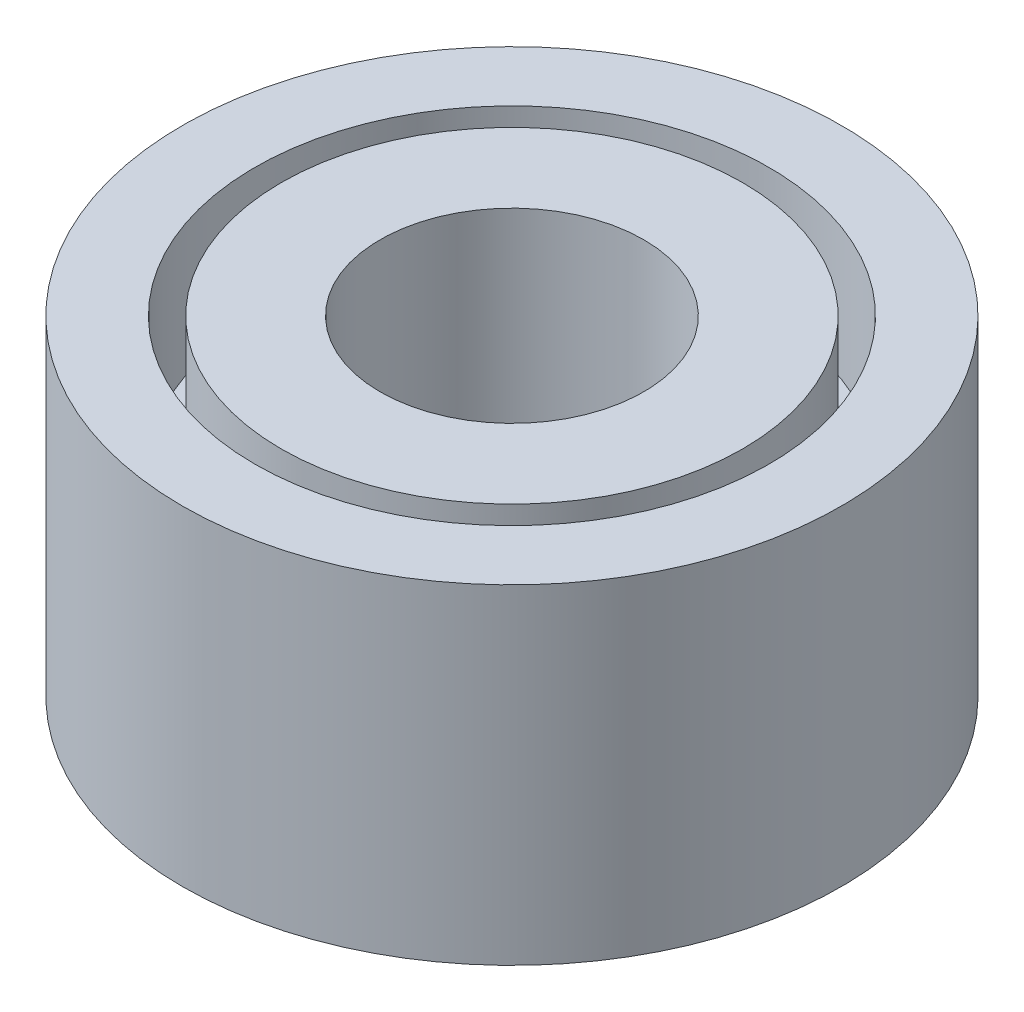
SolidWorks part; units mm, degrees
ref_plane "前视基准面" through (0, 0, 0) normal (0, 0, 1) x (1, 0, 0)
ref_plane "上视基准面" through (0, 0, 0) normal (0, 1, 0) x (1, 0, 0)
ref_plane "右视基准面" through (0, 0, 0) normal (1, 0, 0) x (0, 0, -1)
other "Configuration Table"
sketch "草图1" plane through (0, 0, 0) normal (0, 1, 0) x (1, 0, 0)
  circle A0 centre (0, 0) radius 2.5
  circle A1 centre (0, 0) radius 1
  circle A2 centre (0, 0) radius 1.75
  dimension "D1" = 2
  dimension "D2" = 5
  dimension "D3" = 3.5
extrude "凸台-拉伸1" add sketch "草图1" along normal blind 2.5 contours A1 | A0 region at (0, 0, 0)
extrude "切除-拉伸-薄壁1" cut sketch "草图1<3>" along normal blind 1 thin contours A2 thin type one direction wall 0.2
sketch "草图1<3>" plane through (0, 0, 0) normal (0, 1, 0) x (1, 0, 0) same geometry as "草图1"
extrude "切除-拉伸-薄壁2" cut sketch "草图1<4>" against normal blind 1 from surface thin contours A2 starting at face at (0, 2.5, 2.5) thin type one direction wall 0.2
sketch "草图1<4>" plane through (0, 0, 0) normal (0, 1, 0) x (1, 0, 0) same geometry as "草图1"
